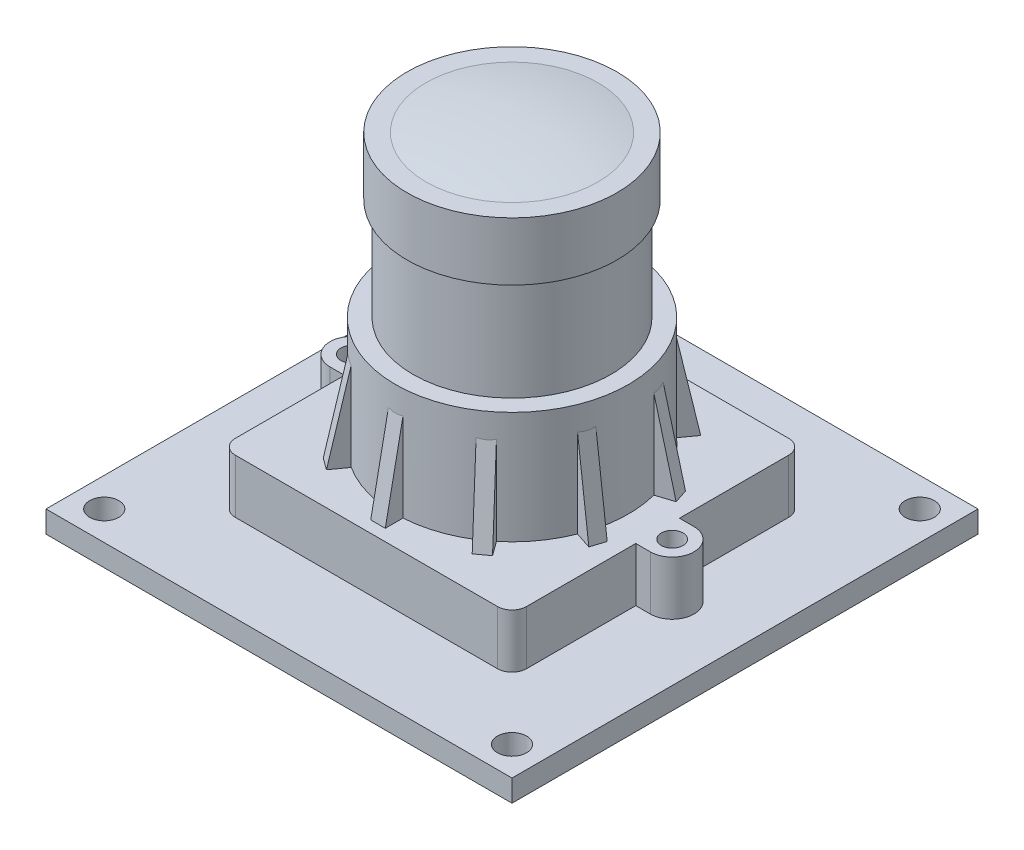
SolidWorks part; units mm, degrees
material "ABS"
ref_plane "前视基准面" through (0, 0, 0) normal (0, 0, 1) x (1, 0, 0)
ref_plane "上视基准面" through (0, 0, 0) normal (0, 1, 0) x (1, 0, 0)
ref_plane "右视基准面" through (0, 0, 0) normal (1, 0, 0) x (0, 0, -1)
sketch "草图1" plane through (0, 0, 0) normal (0, 1, 0) x (1, 0, 0)
  line L0 (0, 16) -> (0, -16) construction
  line L1 (-16, -16) -> (16, -16)
  line L2 (-16, -16) -> (-16, 16)
  line L3 (-16, 16) -> (16, 16)
  line L4 (16, -16) -> (16, 16)
  line L5 (-16, -16) -> (16, 16) construction
  line L6 (-16, 16) -> (16, -16) construction
  line L7 (-16, 0) -> (16, 0) construction
  circle A0 centre (-14, 14) radius 1
  circle A2 centre (14, 14) radius 1
  circle A3 centre (14, -14) radius 1
  circle A4 centre (-14, -14) radius 1
  point P0 (0, 0)
  dimension "D4" = 2
  dimension "D1" = 32
  dimension "D2" = 32
  dimension "D3" = 28
extrude "凸台-拉伸1" add sketch "草图1" along normal blind 1.5
sketch "草图2" plane through (0, 1.5, 0) normal (0, 1, 0) x (1, 0, 0)
  line L0 (0, 10) -> (0, -10) construction
  line L1 (-10, -10) -> (10, -10)
  line L2 (-10, -10) -> (-10, -1.5)
  line L3 (-10, 10) -> (10, 10)
  line L4 (10, -10) -> (10, 10) construction
  line L5 (-10, -10) -> (10, 10) construction
  line L6 (-10, 10) -> (10, -10) construction
  line L7 (-10, 0) -> (10, 0) construction
  line L8 (10, 1.5) -> (11, 1.5)
  line L9 (10, -1.5) -> (11, -1.5)
  line L10 (-10, -1.5) -> (-11, -1.5)
  line L11 (-10, 1.5) -> (-11, 1.5)
  line L12 (-10, 1.5) -> (-10, 10)
  line L13 (10, 1.5) -> (10, 10)
  line L14 (10, -1.5) -> (10, -10)
  arc A0 (11, -1.5) -> (11, 1.5) centre (11, 0) ccw
  circle A1 centre (11, 0) radius 0.75
  circle A2 centre (-11, 0) radius 0.75
  arc A3 (-11, -1.5) -> (-11, 1.5) centre (-11, 0) cw
  point P0 (0, 0)
  dimension "D4" = 1.5
  dimension "D5" = 1.5
  dimension "D1" = 20
  dimension "D2" = 20
  dimension "D3" = 11
extrude "凸台-拉伸2" add sketch "草图2" along normal blind 3.7
sketch "Sketch1" plane through (0, 5.2, 0) normal (0, 1, 0) x (1, 0, 0)
  circle A0 centre (0, 0) radius 8
  dimension "D1" = 16
extrude "Boss-Extrude1" add sketch "Sketch1" along normal blind 7.7
sketch "Sketch4" plane through (0, 0, 0) normal (1, 0, 0) x (0, 0, -1)
  line L0 (8, 11.2) -> (9.2, 5.2)
  line L1 (8, 5.2) -> (8, 12.9) construction
  line L2 (1.5, 5.2) -> (10, 5.2) construction
  dimension "D1" = 6
  dimension "D2" = 1.2
rib "Rib1" sketch "Sketch4" sketch "Sketch4" thickness 1 extrusion direction parallel to sketch draft on no parameters "D1"=1
pattern_circular "CirPattern1" count 10 every 36 about axis through (0, 12.9, 0) along (0, 1, 0) of "Rib1"
sketch "Sketch5" plane through (0, 0, 0) normal (1, 0, 0) x (0, 0, -1)
  line L0 (0, 12.9) -> (0, 27.614) construction
  line L1 (8, 12.9) -> (-8, 12.9) construction
  line L2 (0, 23.9) -> (7.2, 23.9)
  line L3 (7.2, 23.9) -> (7.2, 19.9)
  line L4 (7.2, 19.9) -> (6.8, 19.9)
  line L5 (6.8, 19.9) -> (6.8, 12.9)
  line L6 (6.8, 12.9) -> (0, 12.9)
  line L7 (0, 12.9) -> (0, 23.9)
  dimension "D1" = 7.2
  dimension "D2" = 11
  dimension "D3" = 4
  dimension "D4" = 6.8
revolve "Revolve1" add sketch "Sketch5" angle 360 about L0
fillet "Fillet1" radius 1 4 edges at (-10, 3.35, 10) (10, 3.35, 10) (-10, 3.35, -10) (10, 3.35, -10)
sketch "Sketch6" plane through (0, 0, 0) normal (0, 0, 1) x (1, 0, 0)
  line L0 (7.2, 23.9) -> (-7.2, 23.9) construction
  line L1 (-5.907, 23.9) -> (0, 23.9)
  line L2 (0, 24.4699) -> (0, 23.9)
  circle A0 centre (0, -6.4301) radius 30.9 construction
  arc A1 (-5.907, 23.9) -> (0, 24.4699) centre (0, -6.4301) cw
  dimension "D1" = 61.8
  dimension "D2" = 6.4301
revolve "Revolve3" add sketch "Sketch6" angle 360 about L2
